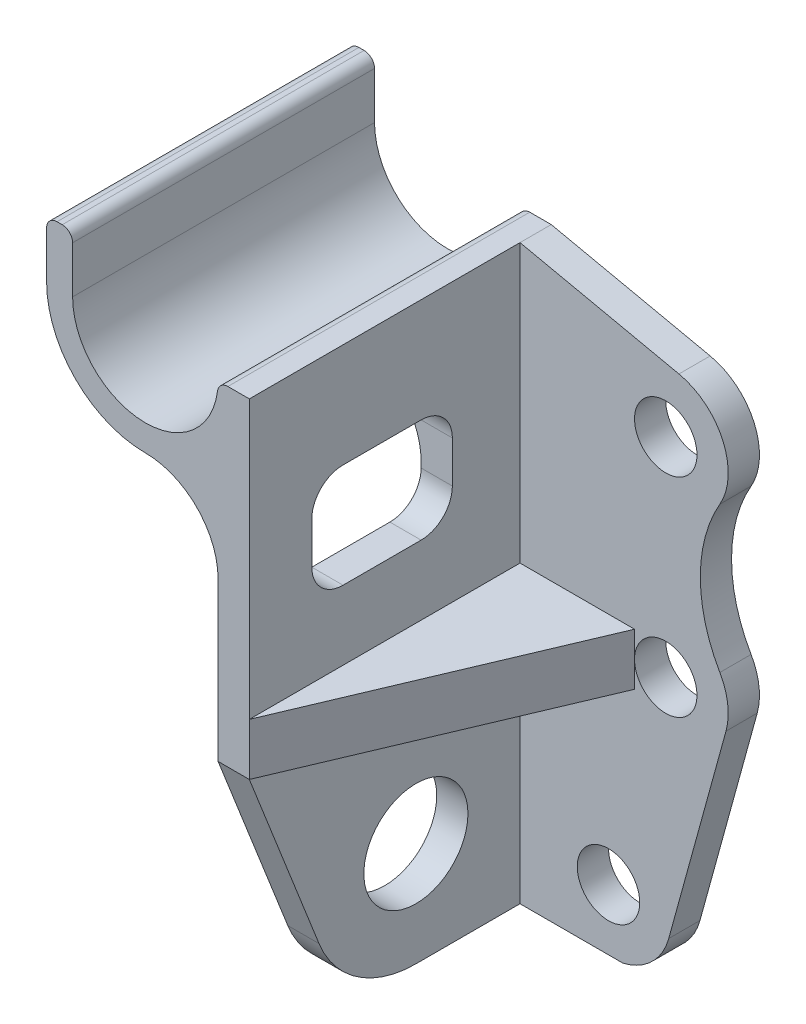
SolidWorks part; units mm, degrees
ref_plane "Front Plane" through (0, 0, 0) normal (0, 0, 1) x (1, 0, 0)
ref_plane "Top Plane" through (0, 0, 0) normal (0, 1, 0) x (1, 0, 0)
ref_plane "Right Plane" through (0, 0, 0) normal (1, 0, 0) x (0, 0, -1)
sketch "Sketch1" plane through (0, 0, 0) normal (0, 0, 1) x (1, 0, 0)
  line L4 (-18.9739, 0) -> (-18.9739, 9)
  line L8 (19.9739, 0) -> (19.9739, -110)
  line L9 (-16.9739, 11) -> (-15.9739, 11)
  line L10 (-13.9739, 9) -> (-13.9739, 0)
  line L12 (19.9739, -110) -> (15.9739, -110)
  line L13 (13.9739, -108) -> (13.9739, -32.9739)
  line L16 (15.8482, 0) -> (19.9739, 0)
  line L17 (19.9739, 0) -> (50.5057, -6.5901)
  line L18 (19.9739, -110) -> (39.7265, -110)
  line L19 (48.5444, -101.5018) -> (59.5444, -61.5018)
  arc A9 (-18.9739, 0) -> (-0.015, -18.9739) centre (0, 0) ccw
  arc A10 (-13.9739, 0) -> (13.8639, -1.7496) centre (0, 0) ccw
  arc A12 (13.9739, -32.9739) -> (-0.015, -18.9739) centre (-0.0261, -32.9739) ccw
  arc A13 (58.3662, -24.32) -> (50.5057, -6.5901) centre (47.9739, -18.32) ccw
  circle A14 centre (47.9739, -18.32) radius 6
  arc A15 (59.5444, -61.5018) -> (58.3662, -52.32) centre (47.9739, -58.32) ccw
  circle A16 centre (47.9739, -58.32) radius 6
  arc A17 (39.7265, -110) -> (48.5444, -101.5018) centre (36.9739, -98.32) ccw
  circle A18 centre (36.9739, -98.32) radius 6
  arc A20 (58.3662, -24.32) -> (58.3662, -52.32) centre (82.6149, -38.32) ccw
  arc A21 (15.8482, 0) -> (13.8639, -1.7496) centre (15.8482, -2) ccw
  arc A22 (15.9739, -110) -> (13.9739, -108) centre (15.9739, -108) cw
  arc A23 (-15.9739, 11) -> (-13.9739, 9) centre (-15.9739, 9) cw
  arc A24 (-18.9739, 9) -> (-16.9739, 11) centre (-16.9739, 9) cw
  point P33 (13.9739, 0)
  point P36 (13.9739, -110)
  point P39 (-13.9739, 11)
  point P42 (-18.9739, 11)
  dimension "D1" = 6
  dimension "D2" = 6
  dimension "D3" = 11
  dimension "D4" = 28
  dimension "D5" = 5
  dimension "D6" = 28
  dimension "D7" = 12
  dimension "D8" = 24
  dimension "D10" = 24
  dimension "D11" = 12
  dimension "D13" = 12
  dimension "D15" = 24
  dimension "D16" = 56
  dimension "D18" = 2
  dimension "D9" = 110
  dimension "D12" = 40
  dimension "D14" = 17
  dimension "D19" = 40
extrude "Boss-Extrude1" add sketch "Sketch1" along normal blind 58 contours A24 L4 A9 A13 L13 A22 L12 L8 L16 A21 A10 L10 A23 L9 region at (-17.7028, 4.5, 0)
extrude "Boss-Extrude3" add sketch "Sketch1<4>" along normal blind 6 contours A20 A13 L17 L8 L18 A17 L19 A15 A18 A16 A14 region at (36.8699, -54.0593, 0)
sketch "Sketch1<4>" plane through (0, 0, 0) normal (0, 0, 1) x (1, 0, 0) same geometry as "Sketch1"
sketch "Sketch6" plane through (19.9739, 0, 0) normal (1, 0, 0) x (0, 0, -1)
  line L0 (-40, -40) -> (-25, -40)
  line L1 (-46, -34) -> (-46, -26)
  line L2 (-40, -20) -> (-25, -20)
  line L3 (-19, -34) -> (-19, -26)
  line L4 (-58, 0) -> (-58, -110) construction
  arc A0 (-40, -40) -> (-46, -34) centre (-40, -34) cw
  arc A1 (-25, -40) -> (-19, -34) centre (-25, -34) ccw
  arc A2 (-25, -20) -> (-19, -26) centre (-25, -26) cw
  arc A3 (-46, -26) -> (-40, -20) centre (-40, -26) cw
  point P14 (-40, -16.8491)
  point P15 (-25, -22.6919)
  dimension "D1" = 6
  dimension "D2" = 12
  dimension "D3" = 15
  dimension "D4" = 20
  dimension "D5" = 20
  dimension "D6" = 27
extrude "Cut-Extrude8" cut sketch "Sketch6" against normal blind 26 contours L2 A2 L3 A1 L0 A0 L1 A3
ref_plane "Plane1" through (0, -58.32, 0) normal (0, 1, 0) x (1, 0, 0)
sketch "Sketch8" plane through (0, -58.32, 0) normal (0, 1, 0) x (1, 0, 0)
  line L0 (19.9739, -58) -> (41.9739, -6)
  line L1 (19.9739, -6) -> (50.5057, -6) construction
  dimension "D1" = 22
rib "Rib14" sketch "Sketch8" sketch "Sketch8" thickness 10 extrusion direction parallel to sketch draft on no parameters "D1"=10
sketch "Sketch10" plane through (19.9739, 0, 0) normal (1, 0, 0) x (0, 0, -1)
  line L0 (-58, -110) -> (-6, -110) construction
  line L1 (-44.6093, -97.3275) -> (-58, -63.32)
  circle A0 centre (-26, -90) radius 20
  circle A1 centre (-26, -90) radius 10
  line M5 (-58, -63.32) -> (-58, -110)
  line M6 (-58, -110) -> (-6, -110)
  dimension "D1" = 40
  dimension "D3" = 20
  dimension "D2" = 26
extrude "Cut-Extrude10" cut sketch "Sketch10" against normal blind 21 contours A0 L1 M5 M6 | A1 region at (19.9739, -95.3652, 50.8595) region at (19.9739, -90, 26)
